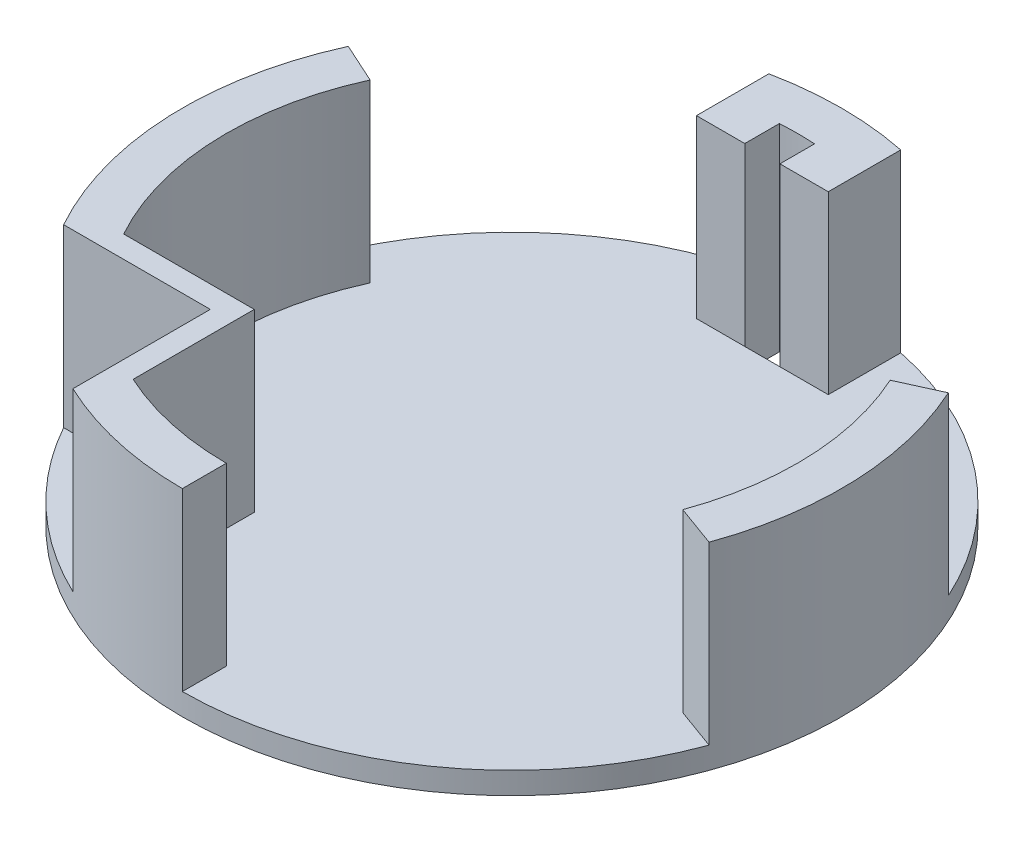
SolidWorks part; units mm, degrees
ref_plane "Front Plane" through (0, 0, 0) normal (0, 0, 1) x (1, 0, 0)
ref_plane "Top Plane" through (0, 0, 0) normal (0, 1, 0) x (1, 0, 0)
ref_plane "Right Plane" through (0, 0, 0) normal (1, 0, 0) x (0, 0, -1)
sketch "Sketch1" plane through (0, 0, 0) normal (0, 1, 0) x (1, 0, 0)
  circle A0 centre (-5.9358, 0) radius 75
  dimension "D1" = 150
extrude "Boss-Extrude1" add sketch "Sketch1" along normal blind 5
sketch "Sketch2" plane through (0, 5, 0) normal (0, 1, 0) x (1, 0, 0)
  line L16 (47.8485, -36.5) -> (26.2006, -36.5)
  line L17 (26.2006, -36.5) -> (26.2006, -56.5)
  line L18 (-5.9358, 0) -> (-80.9358, 0)
  line L19 (-5.9358, 0) -> (69.0642, 0)
  line L20 (-60.9358, 0) -> (-60.9358, 25)
  line L21 (-5.9358, 0) -> (-74.2133, 31.0352)
  line L22 (-60.9358, 0) -> (-60.9358, -20)
  line L23 (-5.9358, 0) -> (-76.4203, -25.6307)
  line L24 (21.2006, -69.9186) -> (21.2006, -31.5)
  line L25 (21.2006, -31.5) -> (62.1285, -31.5)
  line L26 (-5.9358, 0) -> (-5.9358, -75)
  line L27 (47.8485, -36.5) -> (59.5833, -36.5)
  line L28 (26.2006, -56.5) -> (26.2006, -67.7661)
  line L29 (49.0642, 0) -> (49.0642, 25)
  line L30 (-5.9358, 0) -> (62.3417, 31.0352)
  line L31 (-20.9489, 57) -> (-20.9489, 73.482)
  line L32 (9.0511, 57) -> (9.0511, 73.4874)
  line L33 (-20.9489, 57) -> (9.0511, 57)
  line L34 (-9.9489, 64.876) -> (-9.9489, 57)
  line L35 (-1.9489, 64.8776) -> (-1.9489, 57)
  line L36 (-5.9358, 0) -> (64.5487, -25.6307)
  line L37 (49.0642, 0) -> (49.0642, -20)
  line L38 (21.2006, -31.5) -> (-74.0001, -31.5)
  line L39 (26.2006, -36.5) -> (-71.4549, -36.5)
  line L40 (-38.0722, -36.5) -> (-38.0722, -56.5)
  line L41 (-33.0722, -31.5) -> (-33.0722, -69.9186)
  line L42 (-38.0722, -56.5) -> (-38.0722, -67.7661)
  circle A0 centre (-5.9358, 0) radius 75 construction
  circle A1 centre (-5.9358, 0) radius 65
  circle M9 centre (-5.9358, 0) radius 75
  dimension "D3" = 130
  dimension "D4" = 5
  dimension "D1" = 20
  dimension "D2" = 5
  dimension "D5" = 20
  dimension "D6" = 21.6479
  dimension "D8" = 20
extrude "Cut-Extrude1" cut sketch "Sketch2" against normal blind 10 contours L35 A1 L34 L33 region at (-5.9488, 5, -60.9796)
extrude "Boss-Extrude3" add sketch "Sketch2<5>" along normal blind 40 contours A1 L19 L30 M9 | A1 L36 L19 M9 | A1 L41 L26 M9 | A1 L42 L41 M9 | L40 A1 L41 L39 | L38 A1 L39 L41 | A1 L38 L39 M9 | A1 L23 L38 M9 | A1 L18 L23 M9 | A1 L21 L18 M9 | L34 A1 L31 L33 | A1 L32 L31 M9 | L32 A1 L35 L33 region at (62.7703, 5, 12.1043) region at (-19.6873, 5, 68.1548) region at (62.0754, 5, -14.7319) region at (-35.5222, 5, 47.1767) region at (-47.2043, 5, 33.9547) region at (-35.5878, 5, 63.3457) region at (-67.0268, 5, 34.0192) region at (-69.755, 5, 27.6795) region at (-5.9491, 5, -69.4542) region at (3.3447, 5, -60.6275) region at (-74.6419, 5, 12.1043) region at (-73.9471, 5, -14.7319) region at (-15.2418, 5, -60.6256)
sketch "Sketch2<5>" plane through (0, 5, 0) normal (0, 1, 0) x (1, 0, 0) same geometry as "Sketch2"
